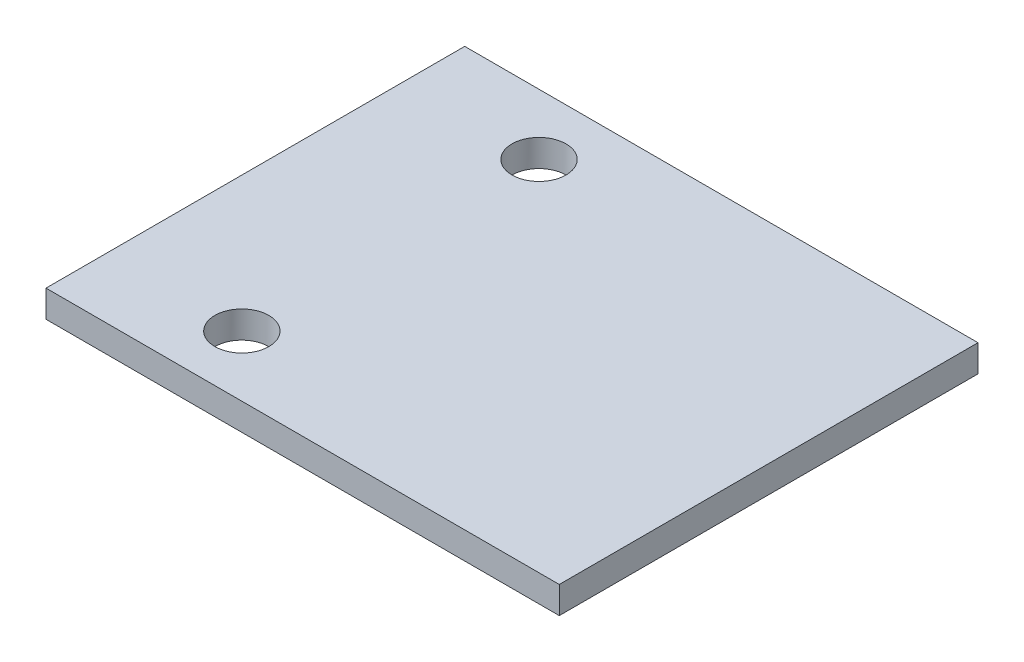
SolidWorks part; units mm, degrees
ref_plane "Front Plane" through (0, 0, 0) normal (0, 0, 1) x (1, 0, 0)
ref_plane "Top Plane" through (0, 0, 0) normal (0, 1, 0) x (1, 0, 0)
ref_plane "Right Plane" through (0, 0, 0) normal (1, 0, 0) x (0, 0, -1)
sketch "Sketch1" plane through (0, 0, 0) normal (0, 1, 0) x (1, 0, 0)
  line L0 (-11.8013, -7.9901) -> (7.1987, -7.9901)
  line L1 (-11.8013, -7.9901) -> (-11.8013, 7.5099)
  line L2 (7.1987, -7.9901) -> (7.1987, 7.5099)
  line L3 (-11.8013, 7.5099) -> (7.1987, 7.5099)
  dimension "D1" = 19
  dimension "D2" = 15.5
extrude "Boss-Extrude1" add sketch "Sketch1" along normal blind 1
hole_wizard "Ø1.0mm Dowel Hole1" positions "Sketch2" profile "Sketch3" hole size "Ø1.0" standard "ANSI Metric"
sketch "Sketch2" plane through (0, 1, 0) normal (0, 1, 0) x (1, 0, 0)
  line L0 (-11.8013, 7.5099) -> (-11.8013, -7.9901) construction
  line L1 (-11.8013, -7.9901) -> (7.1987, -7.9901) construction
  point P0 (-6.8013, 5.2599)
  point P2 (-6.8013, -5.7401)
  dimension "D1" = 11
  dimension "D2" = 5
  dimension "D3" = 2.25
sketch "Sketch3" plane through (-6.8013, 1, -5.2599) normal (1, 0, 0) x (0, 0, 1)
  line L0 (0, 0) -> (0, 25.6009)
  line L1 (0, 25.6009) -> (1, 25)
  line L2 (1, 25) -> (1, 0)
  line L5 (1, 0) -> (0, 0)
  line L10 (0, 25.6009) -> (-1, 25) construction
  line L11 (0, -6.35) -> (0, 107.95) construction
  dimension "Hole Dia." = 2
  dimension "Hole Depth" = 25
  dimension "Drill Angle" = 118
